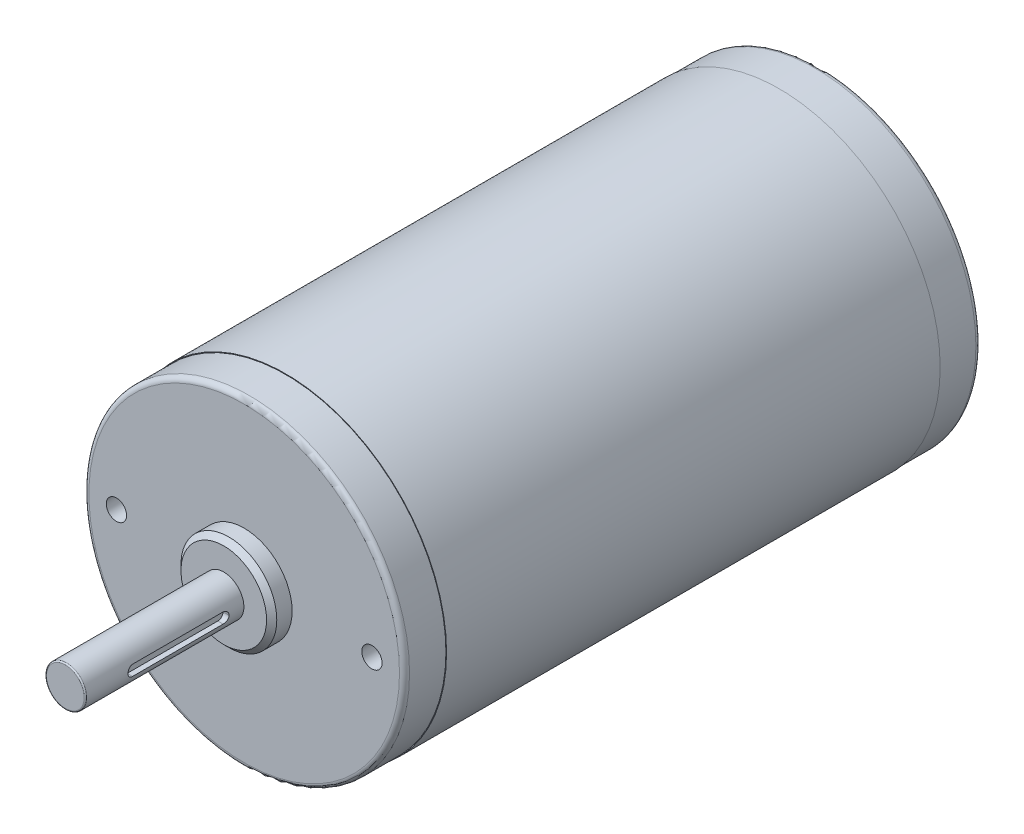
SolidWorks part; units mm, degrees
material "CIM"
ref_plane "Front Plane" through (0, 0, 0) normal (0, 0, 1) x (1, 0, 0)
ref_plane "Top Plane" through (0, 0, 0) normal (0, 1, 0) x (1, 0, 0)
ref_plane "Right Plane" through (0, 0, 0) normal (1, 0, 0) x (0, 0, -1)
ref_plane "Plane1" through (0, 109.2962, 0) normal (0, -1, 0) x (1, 0, 0)
sketch "Sketch1" plane through (0, 109.2962, 0) normal (0, -1, 0) x (1, 0, 0)
  line L0 (67.564, 10.8204) -> (35.56, 10.8204)
  line L1 (35.56, 10.8204) -> (35.56, -87.3252)
  line L2 (35.56, -87.3252) -> (67.564, -87.3252)
  line L3 (67.564, -87.3252) -> (67.564, 10.8204)
  line L4 (35.56, 10.8204) -> (35.56, -87.3252) construction
revolve "Revolve1" add sketch "Sketch1" angle 360 about L4 reverse direction yes
sketch "Sketch2" plane through (0, 0, 10.8204) normal (0, 0, 1) x (1, 0, 0)
  circle A0 centre (35.56, 109.2962) radius 31.877
extrude "Boss-Extrude1" add sketch "Sketch2" along normal blind 8.2296
ref_plane "Plane2" through (0, 0, 18.542) normal (0, 0, -1) x (-1, 0, 0)
sketch "Sketch5" plane through (0, 0, 18.542) normal (0, 0, -1) x (-1, 0, 0)
  circle A0 centre (-35.56, 109.2962) radius 9.525
extrude "Boss-Extrude2" add sketch "Sketch5" against normal blind 4.572
sketch "Sketch6" plane through (0, 0, 23.114) normal (0, 0, 1) x (1, 0, 0)
  circle A0 centre (35.56, 109.2962) radius 4
extrude "Boss-Extrude3" add sketch "Sketch6" along normal blind 31.5
sketch "Sketch8" plane through (0, 0, -87.3252) normal (0, 0, -1) x (-1, 0, 0)
  circle A0 centre (-35.56, 109.2962) radius 31.877
extrude "Boss-Extrude4" add sketch "Sketch8" along normal blind 8.2296
sketch "Sketch9" plane through (0, 0, -95.5548) normal (0, 0, -1) x (-1, 0, 0)
  circle A0 centre (-35.56, 109.2962) radius 15.0368
extrude "Boss-Extrude5" add sketch "Sketch9" along normal blind 4.7625
ref_plane "Plane3" through (0, 120.5036, 0) normal (0, 1, 0) x (-1, 0, 0)
sketch "Sketch10" plane through (0, 120.5036, 0) normal (0, 1, 0) x (-1, 0, 0)
  line L0 (-56.2851, -97.8027) -> (-54.1671, -97.8027)
  line L1 (-54.1671, -97.8027) -> (-54.1671, -95.5548)
  line L2 (-54.1671, -95.5548) -> (-58.4851, -95.5548)
  line L3 (-58.4851, -95.5548) -> (-58.4851, -95.6027)
  line L4 (-58.4851, -95.6027) -> (-56.2851, -97.8027)
  line L5 (-54.1671, -97.8027) -> (-54.1671, -95.5548) construction
revolve "Revolve2" add sketch "Sketch10" angle 360 about L5 reverse direction yes
ref_plane "Plane4" through (0, 127.9033, 0) normal (0, 1, 0) x (-1, 0, 0)
sketch "Sketch11" plane through (0, 127.9033, 0) normal (0, 1, 0) x (-1, 0, 0)
  line L0 (-48.8854, -97.8027) -> (-46.7674, -97.8027)
  line L1 (-46.7674, -97.8027) -> (-46.7674, -95.5548)
  line L2 (-46.7674, -95.5548) -> (-51.0854, -95.5548)
  line L3 (-51.0854, -95.5548) -> (-51.0854, -95.6027)
  line L4 (-51.0854, -95.6027) -> (-48.8854, -97.8027)
  line L5 (-46.7674, -97.8027) -> (-46.7674, -95.5548) construction
revolve "Revolve3" add sketch "Sketch11" angle 360 about L5 reverse direction yes
hole_wizard "Hole2" positions "Sketch13" profile "Sketch12" legacy
sketch "Sketch13" plane through (0, 0, 19.05) normal (0, 0, 1) x (1, 0, 0)
  point P0 (60.96, 109.2962)
sketch "Sketch12" plane through (60.96, 109.2962, 19.05) normal (1, 0, 0) x (0, -1, 0)
  line L0 (0, 0) -> (0, 14.8277)
  line L1 (0, 14.8277) -> (2.0193, 13.6144)
  line L2 (2.0193, 13.6144) -> (2.0193, 0)
  line L4 (2.0193, 0) -> (0, 0)
  line L6 (0, 14.8277) -> (-2.0193, 13.6144) construction
  line L7 (0, -4.2442) -> (0, 117.3081) construction
  dimension "Diameter" = 4.0386
  dimension "Depth" = 13.6144
  dimension "Drill Angle" = 118
hole_wizard "Hole3" positions "Sketch15" profile "Sketch14" legacy
sketch "Sketch15" plane through (0, 0, 19.05) normal (0, 0, 1) x (1, 0, 0)
  point P0 (10.16, 109.2962)
sketch "Sketch14" plane through (10.16, 109.2962, 19.05) normal (1, 0, 0) x (0, -1, 0)
  line L0 (0, 0) -> (0, 14.8277)
  line L1 (0, 14.8277) -> (2.0193, 13.6144)
  line L2 (2.0193, 13.6144) -> (2.0193, 0)
  line L4 (2.0193, 0) -> (0, 0)
  line L6 (0, 14.8277) -> (-2.0193, 13.6144) construction
  line L7 (0, -4.2442) -> (0, 117.3081) construction
  dimension "Diameter" = 4.0386
  dimension "Depth" = 13.6144
  dimension "Drill Angle" = 118
chamfer "Chamfer1" distance 1.016 angle 45 1 edges at (45.085, 109.2962, 23.114) first distance on face at (45.085, 109.2962, 23.114)
fillet "Fillet1" radius 0.254 1 edges at (39.56, 109.2962, 54.614) tangent propagation no
fillet "Fillet2" radius 1 1 edges at (3.683, 109.2962, -95.5548) tangent propagation no
fillet "Fillet3" radius 1 1 edges at (67.437, 109.2962, 19.05) tangent propagation no
fillet "Fillet4" radius 1 1 edges at (20.5232, 109.2962, -100.3173) tangent propagation no
ref_plane "Plane5" through (39.56, 0, 0) normal (1, 0, 0) x (0, 0, -1)
sketch "Sketch16" plane through (39.56, 0, 0) normal (1, 0, 0) x (0, 0, -1)
  line L0 (-26.05, 109.2962) -> (-23.114, 109.2962)
  line L1 (-26.05, 110.3462) -> (-46.15, 110.3462)
  line L2 (-26.05, 110.3462) -> (-26.05, 108.2462)
  line L3 (-26.05, 108.2462) -> (-46.15, 108.2462)
  line L4 (-46.15, 110.3462) -> (-46.15, 108.2462)
  line L5 (-23.114, 113.2962) -> (-23.114, 105.2962) construction
  line L6 (-19.05, 140.1732) -> (-19.05, 78.4192) construction
  dimension "D1" = 7
  dimension "D2" = 2.1
  dimension "D3" = 20.1
extrude "Cut-Extrude2" cut sketch "Sketch16" against normal blind 1.2 contours L1 L4 L3 L2 region at (39.56, 109.2962, 36.1)
fillet "Fillet5" radius 1.05 4 edges at (38.8899, 110.3462, 46.15) (38.8899, 108.2462, 46.15) (38.8899, 108.2462, 26.05) (38.8899, 110.3462, 26.05)
ref_axis "Axis1" through (35.56, 109.2962, 54.36) along (0, 0, -1)
